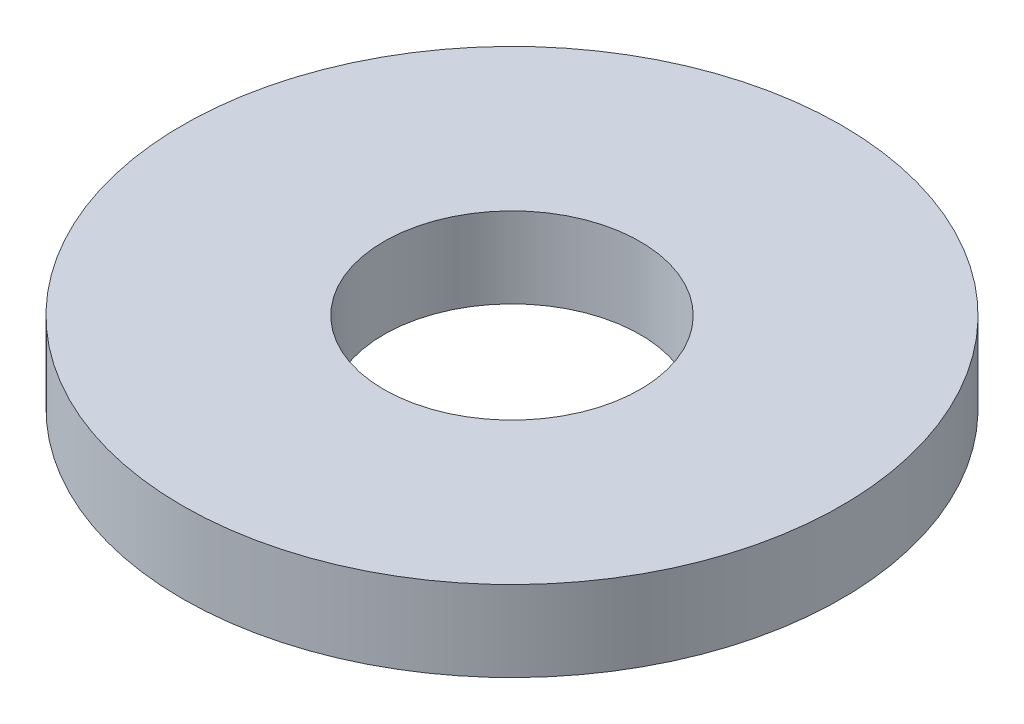
SolidWorks part; units mm, degrees
ref_plane "Front Plane" through (0, 0, 0) normal (0, 0, 1) x (1, 0, 0)
ref_plane "Top Plane" through (0, 0, 0) normal (0, 1, 0) x (1, 0, 0)
ref_plane "Right Plane" through (0, 0, 0) normal (1, 0, 0) x (0, 0, -1)
sketch "Sketch1" plane through (0, 0, 0) normal (0, 1, 0) x (1, 0, 0)
  circle A0 centre (0, 0) radius 45
  dimension "FLANGE_OD" = 90
extrude "Boss-Extrude1" add sketch "Sketch1" along normal blind 11
sketch "Sketch2" plane through (0, 0, 0) normal (0, 1, 0) x (1, 0, 0)
  circle A0 centre (0, 0) radius 17.5
  dimension "BORE_D" = 35
extrude "Cut-Extrude1" cut sketch "Sketch2" along normal through all
sketch "Sketch3" plane through (0, 11, 0) normal (0, 1, 0) x (1, 0, 0)
  circle A0 centre (0, 0) radius 13.2697 construction
  circle A1 centre (-13.2697, 0) radius 4.1721
  dimension "BOLT_D" = 8.3442
  dimension "BOLT_PCD" = 26.5395
extrude "Cut-Extrude2" cut sketch "Sketch3" against normal blind 7.705 rebuild error yes
pattern_circular "CirPattern1" count 5 over 360 rebuild error yes
